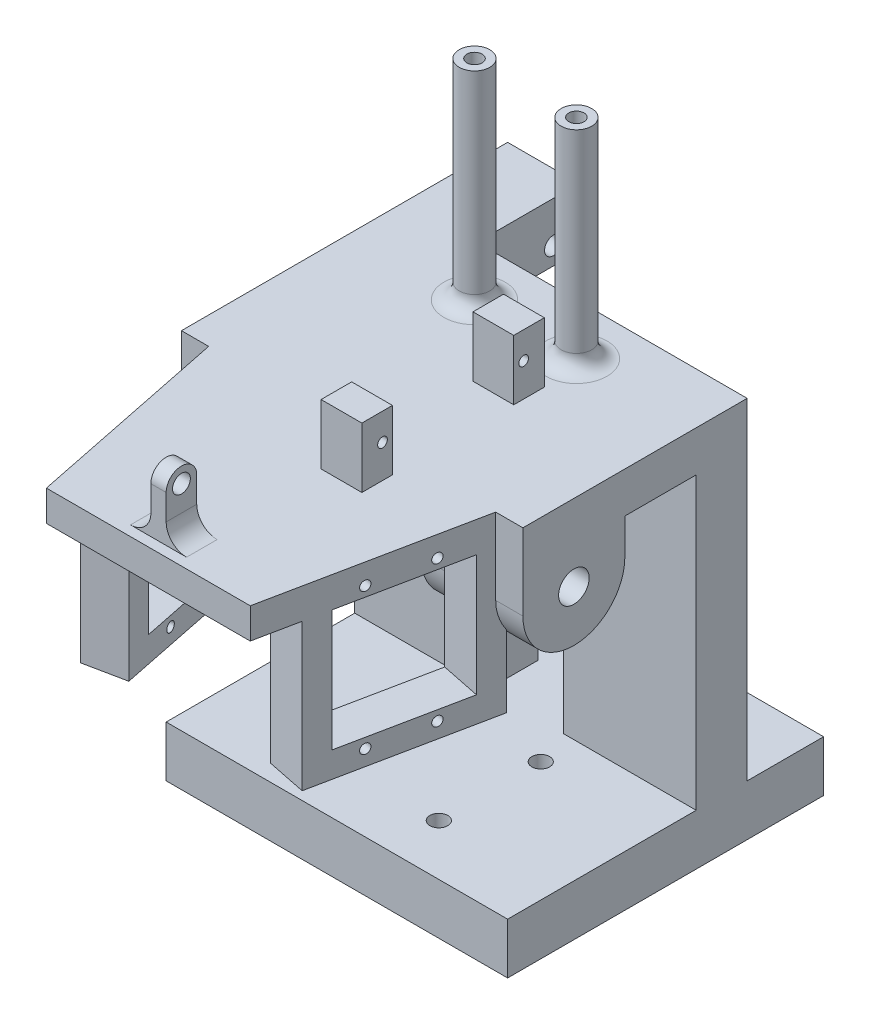
SolidWorks part; units mm, degrees
ref_plane "前视基准面" through (0, 0, 0) normal (0, 0, 1) x (1, 0, 0)
ref_plane "上视基准面" through (0, 0, 0) normal (0, 1, 0) x (1, 0, 0)
ref_plane "右视基准面" through (0, 0, 0) normal (1, 0, 0) x (0, 0, -1)
sketch "草图1" plane through (0, 0, 0) normal (0, 1, 0) x (1, 0, 0)
  line L1 (-33.5, 31) -> (33.5, 31)
  line L2 (-33.5, 31) -> (-33.5, -31)
  line L3 (-33.5, -31) -> (33.5, -31)
  line L4 (33.5, 31) -> (33.5, -31)
  line L5 (-33.5, 31) -> (33.5, -31) construction
  line L6 (-33.5, -31) -> (33.5, 31) construction
  point P0 (0, 0)
  dimension "D1" = 62
  dimension "D2" = 67
extrude "凸台-拉伸1" add sketch "草图1" along normal blind 10
sketch "草图3" plane through (0, 10, 0) normal (0, 1, 0) x (1, 0, 0)
  line L0 (-33.5, 31) -> (-33.5, -31) construction
  line L1 (-33.5, 36) -> (-19.5, 36)
  line L2 (-33.5, 36) -> (-33.5, 16)
  line L3 (-33.5, 16) -> (-19.5, 16)
  line L4 (-19.5, 36) -> (-19.5, 16)
  line L5 (33.5, 31) -> (-33.5, 31) construction
  dimension "D1" = 20
  dimension "D2" = 5
  dimension "D3" = 19.5
extrude "凸台-拉伸2" add sketch "草图3" along normal blind 12.5
sketch "草图4" plane through (-33.5, 0, 0) normal (-1, 0, 0) x (0, 0, 1)
  line L1 (-16, 10) -> (-6, 10)
  line L2 (-16, 10) -> (-16, 75)
  line L3 (-16, 75) -> (-6, 75)
  line L4 (-6, 10) -> (-6, 75)
  dimension "D1" = 10
  dimension "D2" = 65
extrude "凸台-拉伸3" add sketch "草图4" against normal blind 67
sketch "草图5" plane through (0, 75, 0) normal (0, 1, 0) x (1, 0, 0)
  line L0 (33.5, -31) -> (33.5, 6) construction
  line L1 (-33.5, 16) -> (33.5, 16)
  line L2 (-33.5, 16) -> (-33.5, -28)
  line L3 (-33.5, -28) -> (33.5, -28)
  line L4 (33.5, 16) -> (33.5, -28)
  dimension "D1" = 44
extrude "凸台-拉伸4" add sketch "草图5" against normal blind 8
sketch "草图6" plane through (33.5, 0, 0) normal (1, 0, 0) x (0, 0, -1)
  line L0 (6, 10) -> (6, 67) construction
  line L1 (-28, 75) -> (16, 75) construction
  line L2 (-28, 60) -> (-28, 67)
  line L3 (-28, 67) -> (6, 67) construction
  line L5 (-28, 67) -> (-8, 67)
  line L6 (-8, 67) -> (-8, 60)
  arc A0 (-28, 60) -> (-8, 60) centre (-18, 60) ccw
  dimension "D1" = 24
  dimension "D2" = 15
  dimension "D3" = 20
extrude "凸台-拉伸5" add sketch "草图6" against normal blind 20
sketch "草图7" plane through (33.5, 0, 0) normal (1, 0, 0) x (0, 0, -1)
  line L0 (-28, 60) -> (-28, 70.0002)
  line L1 (-28, 60) -> (-28, 75) construction
  line L2 (-28, 70.0002) -> (-8, 70.0002)
  line L3 (-8, 70.0002) -> (-8, 60)
  arc A0 (-28, 60) -> (-8, 60) centre (-18, 60) ccw construction
  arc A1 (-28, 60) -> (-8, 60) centre (-18, 60) ccw
extrude "切除-拉伸1" cut sketch "草图7" against normal blind 8 from offset 6 offset against normal yes
sketch "草图8" plane through (0, 75, 0) normal (0, 1, 0) x (1, 0, 0)
  line L0 (0, -68) -> (20, -68)
  line L2 (20, -68) -> (28.1589, -28)
  line L3 (28.1589, -28) -> (0, -28)
  line L4 (0, -28) -> (0, -68)
  line L5 (-33.5, -28) -> (33.5, -28) construction
  dimension "D1" = 20
  dimension "D2" = 40
extrude "凸台-拉伸6" add sketch "草图8" against normal blind 6
sketch "草图9" plane through (33.5, 0, 0) normal (1, 0, 0) x (0, 0, -1)
  circle A0 centre (-18, 60) radius 3
  dimension "D1" = 6
extrude "切除-拉伸2" cut sketch "草图9" against normal blind 23
sketch "草图10" plane through (32.5173, 0, 6.6326) normal (0.9798, 0, 0.1999) x (0.1999, 0, -0.9798)
  line L1 (-49, 75) -> (-20, 75)
  line L4 (-20, 75) -> (-20, 40.2)
  line L5 (-20, 40.2) -> (-48, 40.2)
  line L9 (-49, 45.2) -> (-25, 45.2)
  line L10 (-25, 45.2) -> (-25, 69)
  line L11 (-25, 69) -> (-49, 69)
  line L12 (-62.6309, 75) -> (-21.8073, 75) construction
  line L14 (-49, 75) -> (-54, 75)
  line L15 (-62.6309, 75) -> (-21.8073, 75) construction
  line L16 (-49, 69) -> (-49, 45.2)
  line L17 (-48, 40.2) -> (-54, 40.2)
  line L18 (-54, 75) -> (-54, 40.2)
  dimension "D1" = 5
  dimension "D2" = 5
  dimension "D3" = 29
  dimension "D4" = 20
  dimension "D5" = 24
  dimension "D6" = 28
  dimension "D7" = 5
  dimension "D8" = 6
  dimension "D9" = 23.8
extrude "凸台-拉伸7" add sketch "草图10" against normal blind 8
sketch "草图12" plane through (0, 75, 0) normal (0, 1, 0) x (1, 0, 0)
  line L1 (-33.5, 36) -> (-19.5, 36)
  line L2 (-33.5, 36) -> (-33.5, 16)
  line L3 (-33.5, 16) -> (-19.5, 16)
  line L4 (-19.5, 36) -> (-19.5, 16)
extrude "凸台-拉伸8" add sketch "草图12" against normal blind 11.5
sketch "草图13" plane through (24.6787, 0, 5.0338) normal (-0.9798, 0, -0.1999) x (-0.1999, 0, 0.9798)
  line L0 (62.6309, 69) -> (54, 69) construction
  line L7 (25, 69) -> (25, 45.2) construction
  line L8 (25, 45.2) -> (49, 45.2) construction
  circle A0 centre (43.5, 70.95) radius 0.95
  circle A1 centre (31.5, 70.95) radius 0.95
  circle A2 centre (31.5, 43.25) radius 0.95
  circle A3 centre (43.5, 43.25) radius 0.95
  dimension "D2" = 6.5
  dimension "D3" = 1.95
  dimension "D4" = 1.95
  dimension "D5" = 12
  dimension "D6" = 1.9
  dimension "D7" = 1.9
  dimension "D13" = 1.9
  dimension "D14" = 1.9
extrude "切除-拉伸4" cut sketch "草图13" against normal up to surface (8 mm away) up to face at (24.59, 60.3229, 45.4971)
sketch "草图14" plane through (0, 75, 0) normal (0, 1, 0) x (1, 0, 0)
  line L0 (33.5, 6) -> (-33.5, 6) construction
  line L1 (3.7, -2) -> (11.7, -2)
  line L2 (3.7, -2) -> (3.7, -8)
  line L3 (3.7, -8) -> (11.7, -8)
  line L4 (11.7, -2) -> (11.7, -8)
  line L5 (11.7, -31.8) -> (11.7, -37.8)
  line L6 (3.7, -37.8) -> (11.7, -37.8)
  line L7 (3.7, -31.8) -> (3.7, -37.8)
  line L8 (3.7, -31.8) -> (11.7, -31.8)
  dimension "D1" = 11.7
  dimension "D2" = 3.7
  dimension "D3" = 6
  dimension "D4" = 14
  dimension "D5" = 6
  dimension "D6" = 8
  dimension "D7" = 23.8
extrude "凸台-拉伸9" add sketch "草图14" along normal blind 11.8
sketch "草图15" plane through (3.7, 0, 0) normal (-1, 0, 0) x (0, 0, 1)
  line L0 (8, 86.8) -> (8, 75) construction
  line L1 (28, 75) -> (-36, 75) construction
  line L2 (31.8, 75) -> (37.8, 75) construction
  line L3 (31.8, 86.8) -> (31.8, 75) construction
  circle A0 centre (33.75, 81.5) radius 0.95
  circle A1 centre (6.05, 81.5) radius 0.95
  dimension "D1" = 1.95
  dimension "D2" = 1.95
  dimension "D3" = 1.9
  dimension "D4" = 1.9
  dimension "D5" = 6.5
  dimension "D6" = 6.5
extrude "切除-拉伸5" cut sketch "草图15" against normal blind 11.8
sketch "草图16" plane through (0, 75, 0) normal (0, 1, 0) x (1, 0, 0)
  line L1 (-1.5, -60) -> (1.5, -60)
  line L2 (-1.5, -60) -> (-1.5, -66)
  line L3 (-1.5, -66) -> (1.5, -66)
  line L4 (1.5, -60) -> (1.5, -66)
  point P4 (0, -66)
  dimension "D2" = 6
  dimension "D3" = 3
  dimension "D4" = 60
extrude "凸台-拉伸10" add sketch "草图16" along normal blind 12
fillet "圆角1" 2 edges at (0, 87, 66) (0, 87, 60) type full round first side face at (0, 79.8, 66) second side face at (0, 79.8, 60) middle face at (0, 87, 63)
sketch "草图17" plane through (-1.5, 0, 0) normal (-1, 0, 0) x (0, 0, 1)
  circle A0 centre (63, 84) radius 1.75
  arc A1 (66, 84) -> (60, 84) centre (63, 84) ccw construction
  dimension "D1" = 3.5
extrude "切除-拉伸6" cut sketch "草图17" against normal blind 7
sketch "草图18" plane through (0, 75, 0) normal (0, 1, 0) x (1, 0, 0)
  line L0 (33.5, 16) -> (-19.5, 16) construction
  circle A0 centre (10, 6) radius 3
  dimension "D1" = 6
  dimension "D2" = 10
  dimension "D3" = 10
extrude "凸台-拉伸11" add sketch "草图18" along normal blind 41
fillet "圆角2" radius 3 1 edges at (10, 75, -3)
mirror "镜向1" about plane through (0, 0, 0) normal (1, 0, 0) of "圆角2", "凸台-拉伸11", "切除-拉伸4", "凸台-拉伸7", "切除-拉伸2", "凸台-拉伸6", "切除-拉伸1", "凸台-拉伸5"
sketch "草图20" plane through (-33.5, 0, 0) normal (-1, 0, 0) x (0, 0, 1)
  line L0 (-36, 63.5) -> (-16, 63.5) construction
  line L1 (-36, 63.5) -> (-36, 75) construction
  circle A0 centre (-31, 67) radius 1.75
  circle A1 centre (-21, 67) radius 1.75
  circle A2 centre (-31, 19) radius 1.75
  circle A3 centre (-21, 19) radius 1.75
  dimension "D1" = 3.5
  dimension "D2" = 10
  dimension "D3" = 48
  dimension "D4" = 3.5
  dimension "D5" = 5
extrude "切除-拉伸7" cut sketch "草图20" against normal blind 35
sketch "草图21" plane through (0, 0, -16) normal (0, 0, -1) x (-1, 0, 0)
  line L1 (-7.5, 65) -> (7.5, 65)
  line L2 (-7.5, 65) -> (-7.5, 10)
  line L3 (-7.5, 10) -> (7.5, 10)
  line L4 (7.5, 65) -> (7.5, 10)
  line L5 (-33.5, 10) -> (19.5, 10) construction
  point P8 (0, 10)
  dimension "D1" = 15
  dimension "D2" = 55
extrude "切除-拉伸8" cut sketch "草图21" against normal blind 35
sketch "草图24" plane through (0, 10, 0) normal (0, 1, 0) x (1, 0, 0)
  line L0 (-33.5, -31) -> (33.5, -31) construction
  circle A0 centre (-10, -21) radius 1.75
  circle A1 centre (10, -21) radius 1.75
  circle A2 centre (-10, -1) radius 1.75
  circle A3 centre (10, -1) radius 1.75
  point P10 (0, -31)
  dimension "D1" = 20
  dimension "D2" = 20
  dimension "D5" = 10
  dimension "D6" = 3.5
  dimension "D7" = 10
  dimension "D3" = 20
  dimension "D4" = 20
extrude "切除-拉伸11" cut sketch "草图24" against normal blind 18
sketch "草图25" plane through (0, 116, 0) normal (0, 1, 0) x (1, 0, 0)
  circle A0 centre (10, 6) radius 1.5
  circle A1 centre (-10, 6) radius 1.5
  dimension "D1" = 3
  dimension "D2" = 3
extrude "切除-拉伸12" cut sketch "草图25" against normal blind 10
fillet "圆角3" radius 4 2 edges at (-1.5, 75, 63) (1.5, 75, 63)
sketch "草图26" plane through (0, 69, 0) normal (0, -1, 0) x (1, 0, 0)
  line L0 (-33.5, -31) -> (-33.5, 31) construction
  line L1 (-4.9, 63.75) -> (4.9, 63.75)
  line L2 (-4.9, 63.75) -> (-4.9, 60.15)
  line L3 (-4.9, 60.15) -> (4.9, 60.15)
  line L4 (4.9, 63.75) -> (4.9, 60.15)
  line L5 (-4.9, 63.75) -> (4.9, 60.15) construction
  line L6 (-4.9, 60.15) -> (4.9, 63.75) construction
  line L7 (-20, 68) -> (20, 68) construction
  point P0 (0, 61.95)
  dimension "D1" = 9.8
  dimension "D2" = 3.6
  dimension "D3" = 28.6
  dimension "D4" = 4.25
extrude "凸台-拉伸12" add sketch "草图26" along normal blind 1
sketch "草图27" plane through (0, 68, 0) normal (0, -1, 0) x (1, 0, 0)
  line L0 (-20, 68) -> (20, 68) construction
  line L2 (-33.5, -31) -> (-33.5, 31) construction
  circle A0 centre (0, 62) radius 1.4
  point P6 (-27.895, 60.2474)
  dimension "D1" = 2.8
  dimension "D2" = 6
  dimension "D3" = 33.5
extrude "切除-拉伸13" cut sketch "草图27" against normal blind 4
